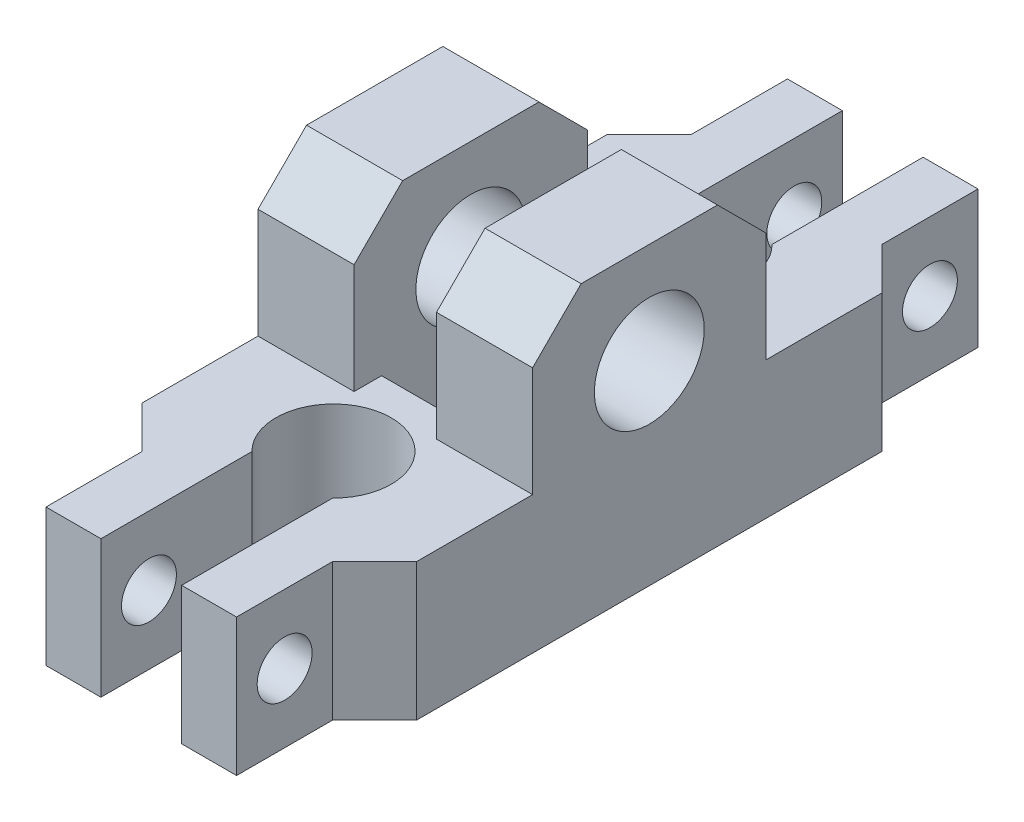
SolidWorks part; units mm, degrees
ref_plane "Front Plane" through (0, 0, 0) normal (0, 0, 1) x (1, 0, 0)
ref_plane "Top Plane" through (0, 0, 0) normal (0, 1, 0) x (1, 0, 0)
ref_plane "Right Plane" through (0, 0, 0) normal (1, 0, 0) x (0, 0, -1)
sketch "Sketch1" plane through (0, 0, 0) normal (0, 1, 0) x (1, 0, 0)
  line L0 (10, 40) -> (10, 33) construction
  line L1 (0, 0) -> (20, 0)
  line L2 (0, 0) -> (0, 40)
  line L3 (0, 40) -> (20, 40)
  line L4 (20, 0) -> (20, 40)
  line L5 (10, 0) -> (10, 7) construction
  line L6 (0, 20) -> (20, 20) construction
  line L7 (12.9394, 0) -> (7.0606, 0)
  line L8 (12.9394, 0) -> (12.9394, 4)
  line L9 (12.9394, 4) -> (7.0606, 4)
  line L10 (7.0606, 0) -> (7.0606, 4)
  line L11 (7.0606, 0) -> (3.0606, 0)
  line L12 (7.0606, 0) -> (7.0606, -7)
  line L13 (7.0606, -7) -> (3.0606, -7)
  line L14 (3.0606, 0) -> (3.0606, -7)
  line L15 (12.9394, 0) -> (16.9394, 0)
  line L16 (12.9394, 0) -> (12.9394, -7)
  line L17 (12.9394, -7) -> (16.9394, -7)
  line L18 (16.9394, 0) -> (16.9394, -7)
  line L19 (7.0606, 47) -> (3.0606, 47)
  line L20 (3.0606, 40) -> (3.0606, 47)
  line L21 (7.0606, 40) -> (3.0606, 40)
  line L22 (7.0606, 40) -> (7.0606, 47)
  line L23 (12.9394, 47) -> (16.9394, 47)
  line L24 (16.9394, 40) -> (16.9394, 47)
  line L25 (12.9394, 40) -> (16.9394, 40)
  line L26 (12.9394, 40) -> (12.9394, 47)
  line L27 (12.9394, 36) -> (7.0606, 36)
  line L28 (7.0606, 40) -> (7.0606, 36)
  line L29 (12.9394, 40) -> (7.0606, 40)
  line L30 (12.9394, 40) -> (12.9394, 36)
  circle A0 centre (10, 33) radius 4.2
  circle A1 centre (10, 7) radius 4.2
  point P11 (10, 4)
  dimension "D1" = 8.4
  dimension "D2" = 26
  dimension "D3" = 40
  dimension "D4" = 20
  dimension "D5" = 4
  dimension "D6" = 4
  dimension "D7" = 7
extrude "Boss-Extrude1" add sketch "Sketch1" along normal blind 10 contours A1 L8 L1 L4 L3 L30 A0 L28 L2 L10 | L18 L1 L16 L17 | L1 L14 L13 L12 | L26 L3 L24 L23 | L3 L22 L19 L20 region at (10, 0, -20) region at (5.0606, 0, 3.5) region at (5.0606, 0, -43.5) region at (14.9394, 0, 3.5) region at (14.9394, 0, -43.5)
sketch "Sketch2" plane through (20, 0, 0) normal (1, 0, 0) x (0, 0, -1)
  line L1 (28.5, 0) -> (11.5, 0)
  line L3 (24.9645, 21.5355) -> (15.0355, 21.5355)
  line L5 (20, 21.5355) -> (20, 0) construction
  line L6 (15.0355, 21.5355) -> (11.5, 21.5355) construction
  line L8 (11.5, 21.5355) -> (11.5, 18) construction
  line L9 (11.5, 18) -> (15.0355, 21.5355)
  line L10 (24.9645, 21.5355) -> (28.5, 18)
  line L11 (28.5, 18) -> (28.5, 0)
  line L12 (11.5, 18) -> (11.5, 0)
  line L13 (24.9645, 21.5355) -> (28.5, 21.5355) construction
  line L14 (28.5, 21.5355) -> (28.5, 18) construction
  line L15 (0, 0) -> (40, 0) construction
  circle A0 centre (20, 14.1905) radius 4
  point P8 (20, 0)
  dimension "D3" = 8
  dimension "D1" = 17
  dimension "D2" = 18
  dimension "D4" = 5
  dimension "D5" = 7.345
extrude "Boss-Extrude2" add sketch "Sketch2" against normal up to surface (20 mm away) up to face at (0, 5, -20)
sketch "Sketch3" plane through (0, 21.5355, 0) normal (0, 1, 0) x (1, 0, 0)
  line L1 (7, 26.5) -> (13, 26.5)
  line L2 (7, 26.5) -> (7, 13.5)
  line L3 (7, 13.5) -> (13, 13.5)
  line L4 (13, 26.5) -> (13, 13.5)
  line L8 (10, 26.5) -> (10, 13.5) construction
  line L9 (0, 15.0355) -> (20, 15.0355) construction
  line L10 (7, 11.5) -> (13, 11.5) construction
  line L11 (7, 28.5) -> (13, 28.5) construction
  line L12 (0, 11.5) -> (20, 11.5) construction
  line L13 (0, 28.5) -> (20, 28.5) construction
  point P12 (10, 15.0355)
  dimension "D1" = 6
  dimension "D2" = 2
  dimension "D3" = 2
extrude "Cut-Extrude1" cut sketch "Sketch3" against normal blind 16
sketch "Sketch4" plane through (0, 0, -11.5) normal (0, 0, 1) x (1, 0, 0)
  line L0 (0, 10) -> (20, 10) construction
  line L1 (7, 10) -> (13, 10)
  line L2 (7, 10) -> (7, 20)
  line L3 (7, 20) -> (13, 20)
  line L4 (13, 10) -> (13, 20)
  line L5 (7, 20) -> (13, 20) construction
  point P6 (10, 10)
  point P9 (10, 10)
  dimension "D1" = 6
extrude "Cut-Extrude2" cut sketch "Sketch4" against normal through all
sketch "Sketch5" plane through (3.0606, 0, 0) normal (-1, 0, 0) x (0, 0, 1)
  line L0 (-20, -0.0187) -> (-20, 30.8761) construction
  line L1 (-47, 0) -> (7, 0) construction
  line L2 (-43.5, 10) -> (-43.5, 0) construction
  line L3 (-40, 10) -> (-47, 10) construction
  line L4 (3.5, 10) -> (3.5, 0) construction
  line L5 (0, 10) -> (7, 10) construction
  circle A0 centre (3.5, 5) radius 2
  circle A1 centre (-43.5, 5) radius 2
  point P10 (-20, 0)
  dimension "D1" = 4
extrude "Cut-Extrude3" cut sketch "Sketch5" against normal through all
sketch "Sketch6" plane through (0, 10, 0) normal (0, 1, 0) x (1, 0, 0)
  line L0 (16.9394, 40) -> (20, 36.9394)
  line L1 (20, 28.5) -> (20, 40) construction
  line L2 (20, 36.9394) -> (20, 40)
  line L3 (20, 40) -> (16.9394, 40)
  line L4 (10, 28.8) -> (10, 26.5) construction
  line L6 (13, 26.5) -> (7, 26.5) construction
  line L7 (0, 40) -> (3.0606, 40)
  line L8 (0, 36.9394) -> (0, 40)
  line L9 (3.0606, 40) -> (0, 36.9394)
  line L10 (12.9394, -7) -> (12.9394, 47) construction
  line L11 (12.9394, 20) -> (-5.4645, 20) construction
  line L12 (3.0606, 0) -> (0, 3.0606)
  line L13 (0, 3.0606) -> (0, 0)
  line L14 (0, 0) -> (3.0606, 0)
  line L15 (20, 0) -> (16.9394, 0)
  line L16 (20, 3.0606) -> (20, 0)
  line L17 (16.9394, 0) -> (20, 3.0606)
  point P10 (10, 26.5)
  point P20 (12.9394, 20)
extrude "Cut-Extrude4" cut sketch "Sketch6" against normal up to surface (10 mm away) up to face at (10, 0, -20)
equation "\"8mm hole\" = 8.4mm"
equation "\"22mm hole\"= 23mm"
equation "\"15mm hole\"= 15.8mm"
equation "\"bed height offset\"= 3mm"
equation "\"motor width\"= 42.5mm"
equation "\"D1@Sketch1\"= \"8mm hole\""
